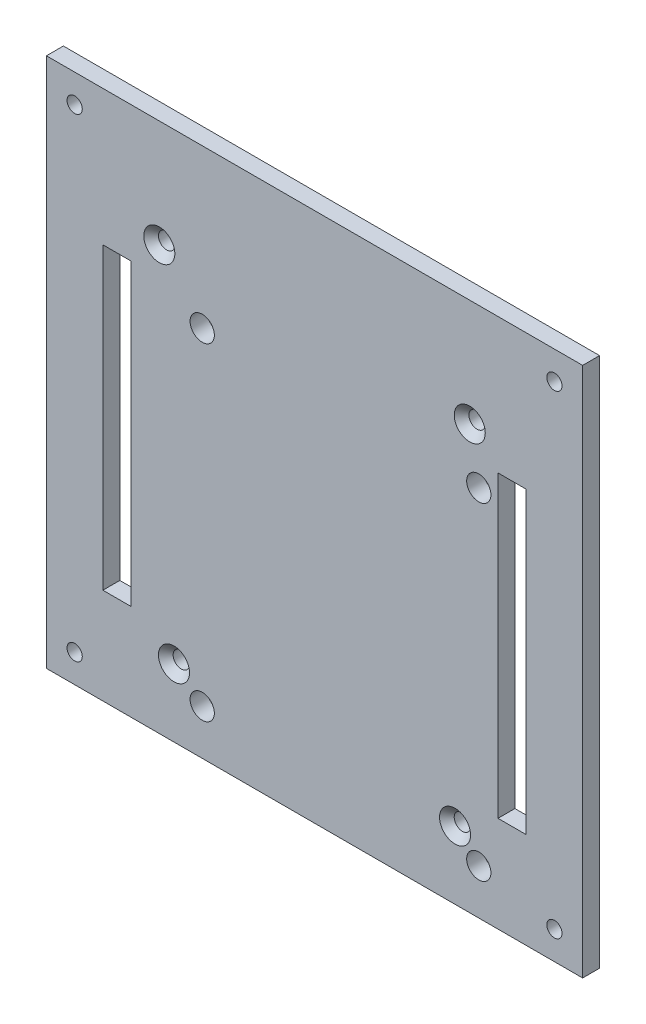
SolidWorks part; units mm, degrees
ref_plane "Alzado" through (0, 0, 0) normal (0, 0, 1) x (1, 0, 0)
ref_plane "Planta" through (0, 0, 0) normal (0, 1, 0) x (1, 0, 0)
ref_plane "Vista lateral" through (0, 0, 0) normal (1, 0, 0) x (0, 0, -1)
sketch "Croquis1" plane through (0, 0, 0) normal (0, 0, 1) x (1, 0, 0)
  line L1 (0, 82) -> (95, 82)
  line L2 (0, 82) -> (0, 0)
  line L3 (0, 0) -> (95, 0)
  line L4 (95, 82) -> (95, 0)
  line L5 (0, 82) -> (95, 82)
  line L9 (0, 0) -> (95, 0)
  dimension "D1" = 95
  dimension "D2" = 82
extrude "Saliente-Extruir1" add sketch "Croquis1" along normal blind 3 contours L1 | L3 | L2 L3 L4 L1 region at (47.5, 41, 0)
sketch "Croquis3" plane through (0, 0, 3) normal (0, 0, 1) x (1, 0, 0)
  line L0 (47.5, 82) -> (47.5, 0) construction
  line L3 (0, 6) -> (95, 6) construction
  line L4 (95, 69) -> (0, 69) construction
  line L5 (20, 0) -> (20, 82) construction
  line L6 (22.6, 0) -> (22.6, 82) construction
  line L7 (72.4, 0) -> (72.4, 82) construction
  line L8 (75, 0) -> (75, 82) construction
  line L15 (0, 82) -> (95, 82) construction
  line L16 (0, 0) -> (95, 0) construction
  line L17 (0, 82) -> (0, 0) construction
  line L18 (95, 82) -> (95, 0) construction
  dimension "D1" = 24.9
  dimension "D2" = 24.9
  dimension "D3" = 27.5
  dimension "D4" = 27.5
  dimension "D5" = 6
  dimension "D6" = 13
hole_wizard "Avellanado para tornillo con cabeza plana avellanada de M2.51" positions "Croquis3D1" profile "Croquis4" countersink size "M2.5" standard "ISO" end condition through all
sketch3d "Croquis3D1"
  line L0 (95, 69, 3) -> (0, 69, 3) construction
  line L1 (20, 0, 3) -> (20, 82, 3) construction
  line L2 (75, 0, 3) -> (75, 82, 3) construction
  line L3 (0, 6, 3) -> (95, 6, 3) construction
  line L4 (72.4, 0, 3) -> (72.4, 82, 3) construction
  line L5 (22.6, 0, 3) -> (22.6, 82, 3) construction
  point P0 (20, 69, 3)
  point P6 (75, 69, 3)
  point P10 (72.4, 6, 3)
  point P16 (22.6, 6, 3)
sketch "Croquis4" plane through (20, 69, 3) normal (1, 0, 0) x (0, -1, 0)
  line L0 (0, 0) -> (0, 3)
  line L1 (0, 3) -> (1.45, 3)
  line L2 (1.45, 3) -> (1.45, 1.3)
  line L3 (1.45, 1.3) -> (2.75, 0)
  line L5 (2.75, 0) -> (0, 0)
  line L6 (-1.45, 1.3) -> (-2.75, 0) construction
  line L11 (0, -6.35) -> (0, 107.95) construction
  dimension "Diámetro de taladro hasta el siguiente" = 2.9
  dimension "Profundidad de taladro hasta el siguiente" = 3
  dimension "Diámetro de avellanado cercano" = 5.5
  dimension "Ángulo de avellanado cercano" = 90
sketch "Croquis6" plane through (0, 0, 3) normal (0, 0, 1) x (1, 0, 0)
  line L1 (10, 64) -> (15, 64)
  line L2 (10, 64) -> (10, 11)
  line L3 (10, 11) -> (15, 11)
  line L4 (15, 64) -> (15, 11)
  line L5 (95, 69) -> (0, 69) construction
  line L6 (0, 6) -> (95, 6) construction
  line L7 (47.5, 82) -> (47.5, 0) construction
  line L8 (0, 82) -> (95, 82) construction
  line L9 (85, 11) -> (80, 11)
  line L10 (85, 64) -> (85, 11)
  line L11 (80, 64) -> (80, 11)
  line L12 (0, 82) -> (0, 0) construction
  line L13 (85, 64) -> (80, 64)
  dimension "D1" = 5
  dimension "D2" = 5
  dimension "D3" = 5
  dimension "D8" = 10
extrude "Cortar-Extruir1" cut sketch "Croquis6" against normal up to next
sketch "Croquis7" plane through (0, 82, 0) normal (0, 1, 0) x (1, 0, 0)
  line L1 (0, 0) -> (95, 0)
  line L2 (0, 0) -> (0, -3)
  line L3 (0, -3) -> (95, -3)
  line L4 (95, 0) -> (95, -3)
extrude "Saliente-Extruir2" add sketch "Croquis7" along normal blind 6
sketch "Croquis8" plane through (0, 0, 0) normal (0, -1, 0) x (1, 0, 0)
  line L1 (0, 3) -> (95, 3)
  line L2 (0, 3) -> (0, 0)
  line L3 (0, 0) -> (95, 0)
  line L4 (95, 3) -> (95, 0)
extrude "Saliente-Extruir3" add sketch "Croquis8" along normal blind 6
sketch "Croquis9" plane through (0, 0, 3) normal (0, 0, 1) x (1, 0, 0)
  line L1 (95, 88) -> (95, -6) construction
  line L3 (95, -6) -> (0, -6) construction
  circle A0 centre (82.5, 4) radius 2.5
  dimension "D1" = 5
  dimension "D3" = 10
  dimension "D2" = 12.5
sketch "Croquis11" plane through (0, 0, 3) normal (0, 0, 1) x (1, 0, 0)
  line L0 (0, 83) -> (95, 83) construction
  line L1 (0, 88) -> (0, -6) construction
  line L2 (95, 88) -> (95, -6) construction
  line L3 (5, 88) -> (5, -6) construction
  line L4 (0, 88) -> (95, 88) construction
  line L5 (95, -6) -> (0, -6) construction
  line L6 (90, 88) -> (90, -6) construction
  line L7 (0, -1) -> (95, -1) construction
  dimension "D1" = 5
  dimension "D2" = 5
  dimension "D3" = 5
  dimension "D4" = 5
hole_wizard "Taladro de margen para M2.51" positions "Croquis3D2" profile "Croquis12" hole size "M2.5" standard "ISO" end condition through all
sketch3d "Croquis3D2"
  line L0 (0, 83, 3) -> (95, 83, 3) construction
  line L1 (5, 88, 3) -> (5, -6, 3) construction
  line L2 (0, -1, 3) -> (95, -1, 3) construction
  line L3 (90, 88, 3) -> (90, -6, 3) construction
  point P0 (5, 83, 3)
  point P6 (5, -1, 3)
  point P10 (90, -1, 3)
  point P14 (90, 83, 3)
sketch "Croquis12" plane through (5, 83, 3) normal (1, 0, 0) x (0, -1, 0)
  line L0 (0, 0) -> (0, 3)
  line L1 (0, 3) -> (1.35, 3)
  line L2 (1.35, 3) -> (1.35, 0)
  line L5 (1.35, 0) -> (0, 0)
  line L11 (0, -6.35) -> (0, 107.95) construction
  dimension "Diámetro de taladro hasta el siguiente" = 2.7
  dimension "Profundidad de taladro hasta el siguiente" = 3
sketch "Croquis13" plane through (0, 0, 3) normal (0, 0, 1) x (1, 0, 0)
  line L0 (27.6, 88) -> (27.6, -6) construction
  line L1 (95, -6) -> (0, -6) construction
  line L2 (76.6, 88) -> (76.6, -6) construction
  line L3 (0, 2) -> (95, 2) construction
  line L4 (0, 88) -> (0, -6) construction
  line L5 (95, 88) -> (95, -6) construction
  line L6 (0, 88) -> (95, 88) construction
  line L7 (0, 60) -> (95, 60) construction
  circle A0 centre (22.6, 6) radius 1.45 construction
  dimension "D1" = 5
  dimension "D2" = 49
  dimension "D3" = 8
  dimension "D4" = 58
hole_wizard "Taladro de margen para M41" positions "Croquis3D3" profile "Croquis14" hole size "M4" standard "ISO" end condition through all
sketch3d "Croquis3D3"
  line L0 (27.6, 88, 3) -> (27.6, -6, 3) construction
  line L1 (0, 2, 3) -> (95, 2, 3) construction
  line L2 (76.6, 88, 3) -> (76.6, -6, 3) construction
  line L3 (0, 60, 3) -> (95, 60, 3) construction
  point P0 (27.6, 2, 3)
  point P6 (76.6, 2, 3)
  point P11 (27.6, 60, 3)
  point P15 (76.6, 60, 3)
sketch "Croquis14" plane through (27.6, 2, 3) normal (1, 0, 0) x (0, -1, 0)
  line L0 (0, 0) -> (0, 3)
  line L1 (0, 3) -> (2.15, 3)
  line L2 (2.15, 3) -> (2.15, 0)
  line L5 (2.15, 0) -> (0, 0)
  line L11 (0, -6.35) -> (0, 107.95) construction
  dimension "Diámetro de taladro hasta el siguiente" = 4.3
  dimension "Profundidad de taladro hasta el siguiente" = 3
